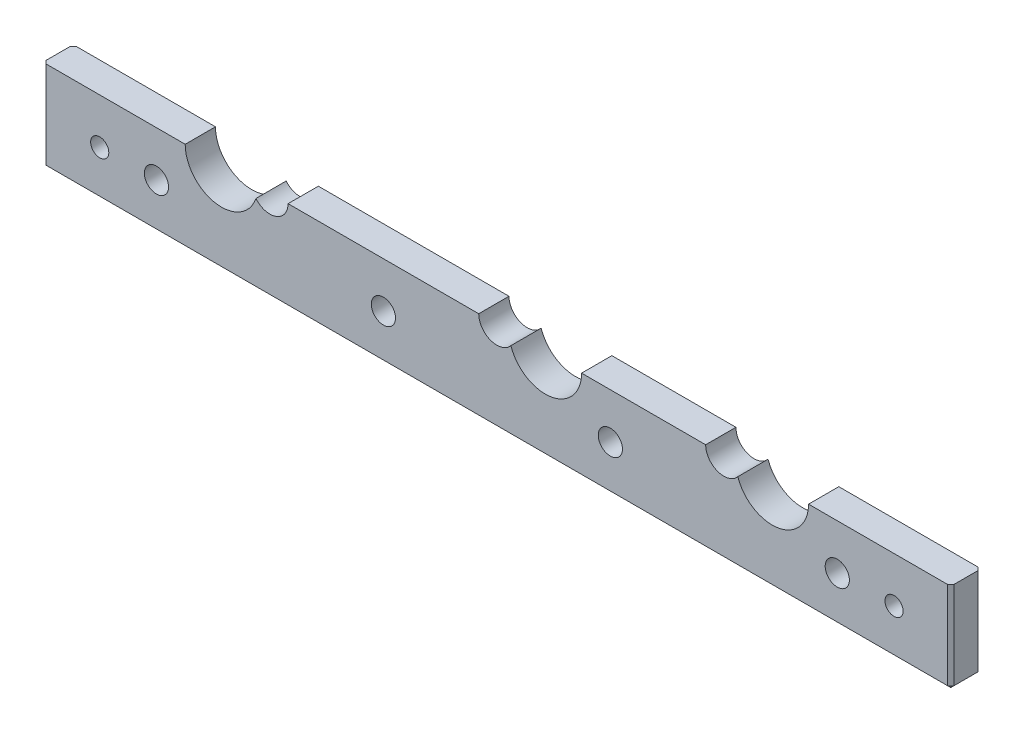
SolidWorks part; units mm, degrees
ref_plane "Front Plane" through (0, 0, 0) normal (0, 0, 1) x (1, 0, 0)
ref_plane "Top Plane" through (0, 0, 0) normal (0, 1, 0) x (1, 0, 0)
ref_plane "Right Plane" through (0, 0, 0) normal (1, 0, 0) x (0, 0, -1)
sketch "Sketch1" plane through (0, 0, 0) normal (0, 0, 1) x (1, 0, 0)
  line L1 (-56.8107, 18.5531) -> (93.1893, 18.5531)
  line L2 (-56.8107, 18.5531) -> (-56.8107, -11.4469)
  line L3 (-56.8107, -11.4469) -> (93.1893, -11.4469)
  line L4 (93.1893, 18.5531) -> (93.1893, -11.4469)
  dimension "D1" = 150
  dimension "D2" = 30
extrude "Boss-Extrude1" add sketch "Sketch1" along normal blind 5 contours L1 L4 L3 L2
sketch "Sketch2" plane through (0, 0, 5) normal (0, 0, 1) x (1, 0, 0)
  line L0 (55.6893, 3.5531) -> (55.6893, 18.5531) construction
  line L2 (93.1893, 18.5531) -> (93.1893, -11.4469) construction
  line L3 (18.1893, 18.5531) -> (18.1893, -11.4469) construction
  line L4 (-56.8107, 18.5531) -> (93.1893, 18.5531) construction
  line L5 (-56.8107, -11.4469) -> (93.1893, -11.4469) construction
  line L6 (18.1893, 3.5531) -> (93.1893, 3.5531) construction
sketch "Sketch3" plane through (0, 0, 0) normal (0, 1, 0) x (1, 0, 0)
  line L0 (18.1893, -5) -> (18.1893, -24.2528) construction
  line L1 (-56.8107, -5) -> (93.1893, -5) construction
ref_plane "Plane1" through (18.1893, 0, 0) normal (-1, 0, 0) x (0, 0, 1)
hole_wizard "Ø6.0mm Dowel Hole1" positions "3DSketch2" profile "Sketch4" hole size "Ø6.0" standard "ISO"
sketch3d "3DSketch2"
  point P0 (55.6893, 3.5531, 5)
  point P3 (18.1893, 3.5531, 5)
sketch "Sketch4" plane through (55.6893, 3.5531, 5) normal (1, 0, 0) x (0, -1, 0)
  line L0 (0, 0) -> (0, 26.8026)
  line L1 (0, 26.8026) -> (3, 25)
  line L2 (3, 25) -> (3, 0)
  line L5 (3, 0) -> (0, 0)
  line L10 (0, 26.8026) -> (-3, 25) construction
  line L11 (0, -6.35) -> (0, 107.95) construction
  dimension "Hole Dia." = 6
  dimension "Hole Depth" = 25
  dimension "Drill Angle" = 118
mirror "Mirror1" about plane through (18.1893, 0, 0) normal (-1, 0, 0) of "Ø6.0mm Dowel Hole1"
sketch "Sketch5" plane through (0, 0, 5) normal (0, 0, 1) x (1, 0, 0)
  line L0 (93.1893, 3.5531) -> (93.1893, 18.5531) construction
  line L1 (93.1893, 18.5531) -> (93.1893, -11.4469) construction
  line L2 (55.6893, 11.0531) -> (18.1893, 11.0531) construction
  line L4 (36.9393, 11.0531) -> (36.9393, 18.5531) construction
  line L5 (55.6893, 11.0531) -> (93.1893, 11.0531) construction
  line L6 (-56.8107, 18.5531) -> (93.1893, 18.5531) construction
  line L7 (74.4393, 11.0531) -> (74.4393, 18.5531) construction
hole_wizard "Ø4.0mm Dowel Hole1" positions "3DSketch3" profile "Sketch6" hole size "Ø4.0" standard "ISO"
sketch3d "3DSketch3"
  point P0 (74.4393, 11.0531, 5)
  point P3 (36.9393, 11.0531, 5)
sketch "Sketch6" plane through (74.4393, 11.0531, 5) normal (1, 0, 0) x (0, -1, 0)
  line L0 (0, 0) -> (0, 26.2017)
  line L1 (0, 26.2017) -> (2, 25)
  line L2 (2, 25) -> (2, 0)
  line L5 (2, 0) -> (0, 0)
  line L10 (0, 26.2017) -> (-2, 25) construction
  line L11 (0, -6.35) -> (0, 107.95) construction
  dimension "Hole Dia." = 4
  dimension "Hole Depth" = 25
  dimension "Drill Angle" = 118
sketch "Sketch7" plane through (0, 0, 0) normal (1, 0, 0) x (0, 0, -1)
  line L0 (-5, 3.5531) -> (-23.0008, 3.5531) construction
  line L1 (-5, 18.5531) -> (-5, -11.4469) construction
ref_plane "Plane2" through (0, 3.5531, 0) normal (0, 1, 0) x (1, 0, 0)
mirror "Mirror2" about plane through (0, 3.5531, 0) normal (0, 1, 0) of "Ø4.0mm Dowel Hole1"
mirror "Mirror3" about plane through (18.1893, 0, 0) normal (-1, 0, 0) of "Mirror2"
sketch "Sketch8" plane through (0, 0, 5) normal (0, 0, 1) x (1, 0, 0)
  line L0 (50.1893, 3.5531) -> (61.1893, 3.5531) construction
  line L1 (55.6893, 3.5531) -> (55.6893, 18.5531) construction
  line L2 (36.9393, 18.5531) -> (36.9393, 3.5531) construction
  line L3 (23.6893, 3.5531) -> (12.6893, 3.5531) construction
  dimension "D1" = 5.5
sketch "Sketch16" plane through (0, 0, 0) normal (0, 0, -1) x (-1, 0, 0)
  line L0 (-50.1893, 13.5531) -> (-49.1893, 13.5531)
  line L1 (-49.1893, 13.5531) -> (-49.1893, 11.5531)
  line L2 (-49.1893, 11.5531) -> (-50.1893, 11.5531)
  line L3 (-50.1893, 11.5531) -> (-50.1893, 13.5531)
sketch "Sketch17" plane through (0, 0, 0) normal (0, 0, -1) x (-1, 0, 0)
  line L0 (-55.6893, 0.5531) -> (-55.6893, -11.4469) construction
  line L1 (-23.6893, -11.4469) -> (-93.1893, -11.4469) construction
  arc A0 (-58.6893, 3.5531) -> (-52.6893, 3.5531) centre (-55.6893, 3.5531) ccw construction
sketch "Sketch18" plane through (0, -11.4469, 0) normal (0, -1, 0) x (1, 0, 0)
  line L0 (55.6893, 0) -> (55.6893, 4.6302) construction
ref_plane "Plane3" through (55.6893, 0, 0) normal (-1, 0, 0) x (0, 0, 1)
sketch "Sketch19" plane through (0, 0, 0) normal (0, 0, -1) x (-1, 0, 0)
  line L0 (-18.1893, 6.5531) -> (-18.1893, 18.5531) construction
  line L1 (13.8107, 18.5531) -> (-50.1893, 18.5531) construction
  arc A0 (-15.1893, 3.5531) -> (-21.1893, 3.5531) centre (-18.1893, 3.5531) ccw construction
sketch "Sketch20" plane through (0, 18.5531, 0) normal (0, 1, 0) x (1, 0, 0)
  line L0 (18.1893, 0) -> (18.1893, -5) construction
  line L1 (-13.8107, 0) -> (50.1893, 0) construction
  line L2 (-13.8107, -5) -> (50.1893, -5) construction
ref_plane "Plane4" through (18.1893, 0, 0) normal (1, 0, 0) x (0, 0, -1)
chamfer "Chamfer1" distance 0.5 angle 45 11 edges at (-56.8107, 18.5531, 2.5) (-56.8107, 3.5531, 5) (-56.8107, -11.4469, 2.5) (-56.8107, 3.5531, 0) (18.1893, -11.4469, 5) (18.1893, -11.4469, 0) (18.1893, 18.5531, 5) (93.1893, 3.5531, 5) (93.1893, -11.4469, 2.5) (93.1893, 3.5531, 0) (18.1893, 18.5531, 0)
sketch "Sketch21" plane through (0, 0, 5) normal (0, 0, 1) x (1, 0, 0)
  line L0 (-56.8107, -10.9469) -> (-56.8107, 18.0531) construction
  line L1 (-56.8107, 3.5531) -> (93.1893, 3.5531)
  line L2 (-56.8107, 3.5531) -> (-56.8107, 18.5531)
  line L3 (-56.8107, 18.5531) -> (93.1893, 18.5531)
  line L4 (93.1893, 3.5531) -> (93.1893, 18.5531)
extrude "Cut-Extrude1" cut sketch "Sketch21" against normal blind 10 contours L2 L3 L4 L1
sketch "Sketch22" plane through (0, 0, 5) normal (0, 0, 1) x (1, 0, 0)
  line L0 (-38.0607, -3.9469) -> (-56.8107, -3.9469) construction
  line L1 (-56.8107, 18.5531) -> (-56.8107, -11.4469) construction
  line L2 (-47.4357, -3.9469) -> (-47.4357, -11.4469) construction
  line L3 (-56.8107, -11.4469) -> (93.1893, -11.4469) construction
hole_wizard "Ø3.0mm Dowel Hole2" positions "3DSketch5" profile "Sketch23" hole size "Ø3.0" standard "ISO"
sketch3d "3DSketch5"
  point P0 (-47.4357, -3.9469, 5)
sketch "Sketch23" plane through (-47.4357, -3.9469, 5) normal (1, 0, 0) x (0, -1, 0)
  line L0 (0, 0) -> (0, 25.9013)
  line L1 (0, 25.9013) -> (1.5, 25)
  line L2 (1.5, 25) -> (1.5, 0)
  line L5 (1.5, 0) -> (0, 0)
  line L10 (0, 25.9013) -> (-1.5, 25) construction
  line L11 (0, -6.35) -> (0, 107.95) construction
  dimension "Hole Dia." = 3
  dimension "Hole Depth" = 25
  dimension "Drill Angle" = 118
mirror "Mirror5" about plane through (18.1893, 0, 0) normal (-1, 0, 0) of "Ø3.0mm Dowel Hole2"
sketch "Sketch24" plane through (0, 0, 5) normal (0, 0, 1) x (1, 0, 0)
  line L0 (58.6893, 3.5531) -> (63.6893, 3.5531) construction
  line L1 (58.6893, 3.5531) -> (92.6893, 3.5531) construction
  dimension "D1" = 5
hole_wizard "Ø12.0mm Dowel Hole1" positions "3DSketch9" profile "Sketch26" hole size "Ø12.0" standard "ISO"
sketch3d "3DSketch9"
  point P0 (63.6893, 3.5531, 5)
sketch "Sketch26" plane through (63.6893, 3.5531, 5) normal (1, 0, 0) x (0, -1, 0)
  line L0 (0, 0) -> (0, 28.6052)
  line L1 (0, 28.6052) -> (6, 25)
  line L2 (6, 25) -> (6, 0)
  line L5 (6, 0) -> (0, 0)
  line L10 (0, 28.6052) -> (-6, 25) construction
  line L11 (0, -6.35) -> (0, 107.95) construction
  dimension "Hole Dia." = 12
  dimension "Hole Depth" = 25
  dimension "Drill Angle" = 118
mirror "Mirror6" about plane through (18.1893, 0, 0) normal (-1, 0, 0) of "Ø12.0mm Dowel Hole1"
sketch "Sketch27" plane through (0, 0, 5) normal (0, 0, 1) x (1, 0, 0)
  line L0 (21.1893, 3.5531) -> (26.1893, 3.5531) construction
  arc A0 (15.1893, 3.5531) -> (21.1893, 3.5531) centre (18.1893, 3.5531) ccw construction
  dimension "D1" = 5
hole_wizard "Ø12.0mm Dowel Hole2" positions "3DSketch11" profile "Sketch29" hole size "Ø12.0" standard "ISO"
sketch3d "3DSketch11"
  point P0 (26.1893, 3.5531, 5)
sketch "Sketch29" plane through (26.1893, 3.5531, 5) normal (1, 0, 0) x (0, -1, 0)
  line L0 (0, 0) -> (0, 28.6052)
  line L1 (0, 28.6052) -> (6, 25)
  line L2 (6, 25) -> (6, 0)
  line L5 (6, 0) -> (0, 0)
  line L10 (0, 28.6052) -> (-6, 25) construction
  line L11 (0, -6.35) -> (0, 107.95) construction
  dimension "Hole Dia." = 12
  dimension "Hole Depth" = 25
  dimension "Drill Angle" = 118
